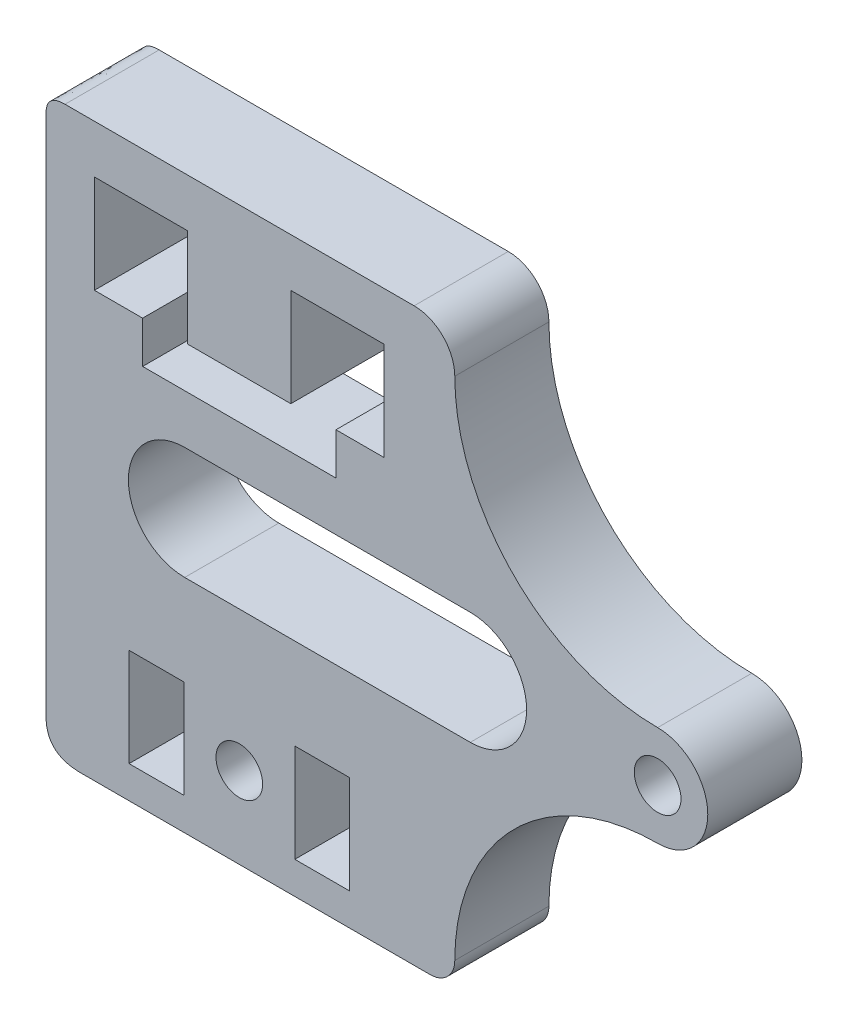
SolidWorks part; units mm, degrees
material "Acrylic (Medium-high impact)"
ref_plane "Front Plane" through (0, 0, 0) normal (0, 0, 1) x (1, 0, 0)
ref_plane "Top Plane" through (0, 0, 0) normal (0, 1, 0) x (1, 0, 0)
ref_plane "Right Plane" through (0, 0, 0) normal (1, 0, 0) x (0, 0, -1)
sketch "Sketch1" plane through (0, 0, 0) normal (0, 0, 1) x (1, 0, 0)
  line L0 (405.5669, 551.1889) -> (405.5669, 553.7889)
  line L1 (396.3551, 553.7889) -> (402.763, 553.7889)
  line L2 (393.5512, 553.7889) -> (393.5512, 551.1889)
  line L3 (393.5512, 551.1889) -> (405.5669, 551.1889)
  line L4 (390.5551, 559.8889) -> (390.5551, 553.7889)
  line L5 (393.5512, 553.7889) -> (390.5551, 553.7889)
  line L6 (396.3551, 559.8889) -> (390.5551, 559.8889)
  line L7 (396.3551, 553.7889) -> (396.3551, 559.8889)
  line L8 (405.5669, 553.7889) -> (408.563, 553.7889)
  line L9 (408.563, 553.7889) -> (408.563, 559.8889)
  line L10 (402.763, 559.8889) -> (402.763, 553.7889)
  line L11 (408.563, 559.8889) -> (402.763, 559.8889)
  line L12 (392.709, 535.4889) -> (392.709, 529.3889)
  line L13 (392.709, 529.3889) -> (396.109, 529.3889)
  line L14 (396.109, 535.4889) -> (392.709, 535.4889)
  line L15 (396.109, 529.3889) -> (396.109, 535.4889)
  line L16 (403.009, 529.3889) -> (406.4091, 529.3889)
  line L17 (406.4091, 529.3889) -> (406.4091, 535.4889)
  line L18 (403.009, 535.4889) -> (403.009, 529.3889)
  line L19 (406.4091, 535.4889) -> (403.009, 535.4889)
  line L20 (388.7281, 562.8889) -> (410.4246, 562.8889)
  line L21 (387.5551, 561.7172) -> (387.5551, 529.5596)
  line L22 (389.7281, 527.3889) -> (411.4246, 527.3889)
  line L23 (-605.591, 535.4889) -> (49394.409, 535.4889) construction
  line L24 (396.1657, 548.1389) -> (413.9157, 548.1389)
  line L25 (396.1657, 541.1389) -> (413.9157, 541.1389)
  line L26 (-600.441, 544.6389) -> (49399.559, 544.6389) construction
  line L27 (398.109, 532.4389) -> (396.109, 532.4389) construction
  line L28 (401.009, 532.4389) -> (403.009, 532.4389) construction
  line L29 (399.559, -466.6171) -> (399.559, 49533.3829) construction
  line L30 (425.559, -455.7473) -> (425.559, 49544.2527) construction
  line L31 (-608.8734, 553.7889) -> (49391.1266, 553.7889) construction
  line L32 (421.909, 544.6389) -> (421.909, 535.4889) construction
  line L33 (421.909, 544.6389) -> (421.909, 553.7889) construction
  line L34 (412.9514, 560.3621) -> (412.9514, 528.9157) construction
  circle A0 centre (425.559, 544.6389) radius 1.45
  arc A1 (396.1657, 548.1389) -> (396.1657, 541.1389) centre (396.1657, 544.6389) ccw
  circle A2 centre (399.559, 532.4389) radius 1.45
  arc A3 (412.9514, 528.9157) -> (425.559, 541.5233) centre (425.559, 528.9157) cw
  arc A4 (412.9514, 560.3621) -> (425.559, 547.7545) centre (425.559, 560.3621) ccw
  arc A5 (425.559, 547.7545) -> (425.559, 541.5233) centre (425.559, 544.6389) cw
  arc A7 (413.9157, 548.1389) -> (413.9157, 541.1389) centre (413.9157, 544.6389) cw
  arc A8 (411.4246, 527.3889) -> (412.9514, 528.9157) centre (411.4246, 528.9157) ccw
  arc A9 (410.4246, 562.8889) -> (412.9514, 560.3621) centre (410.4246, 560.3621) cw
  spline S36 degree 2 poles (387.5551, 561.7172) (387.4906, 562.8889) (388.7281, 562.8889) knots 0 0 0 1 1 1
  spline S37 degree 2 poles (387.5551, 529.5596) (387.4355, 527.3889) (389.7281, 527.3889) knots 0 0 0 1 1 1
  point P26 (399.559, 544.6389)
  point P30 (399.559, 553.7889)
  point P38 (394.409, 535.4889)
  point P40 (412.9514, 544.6389)
  dimension "D5" = 2.9
  dimension "D12" = 6.1
  dimension "D18" = 6.4078
  dimension "D2" = 3.4
  dimension "D3" = 5.8
  dimension "D4" = 2.6
  dimension "D6" = 2
  dimension "D7" = 18.3
  dimension "D8" = 2
  dimension "D9" = 3
  dimension "D10" = 3
  dimension "D11" = 26
  dimension "D13" = 12.0157
  dimension "D15" = 31.4465
  dimension "D17" = 17.75
  dimension "D19" = 13.3924
  dimension "D20" = 22.35
  dimension "D21" = 7
extrude "Boss-Extrude2" add sketch "Sketch1" along normal blind 5.85
sketch "Sketch2" plane through (0, 0, 0) normal (0, 0, 1) x (1, 0, 0)
  line L0 (-600.441, 532.4389) -> (49399.559, 532.4389) construction
  line L1 (406.4091, 529.3889) -> (406.4091, 535.4889) construction
  circle A0 centre (409.6591, 532.4389) radius 1.25
  point P5 (408.4091, 532.4389)
  dimension "D1" = 2.5
  dimension "D2" = 2
extrude "Cut-Extrude1" cut sketch "Sketch2" along normal blind 1
